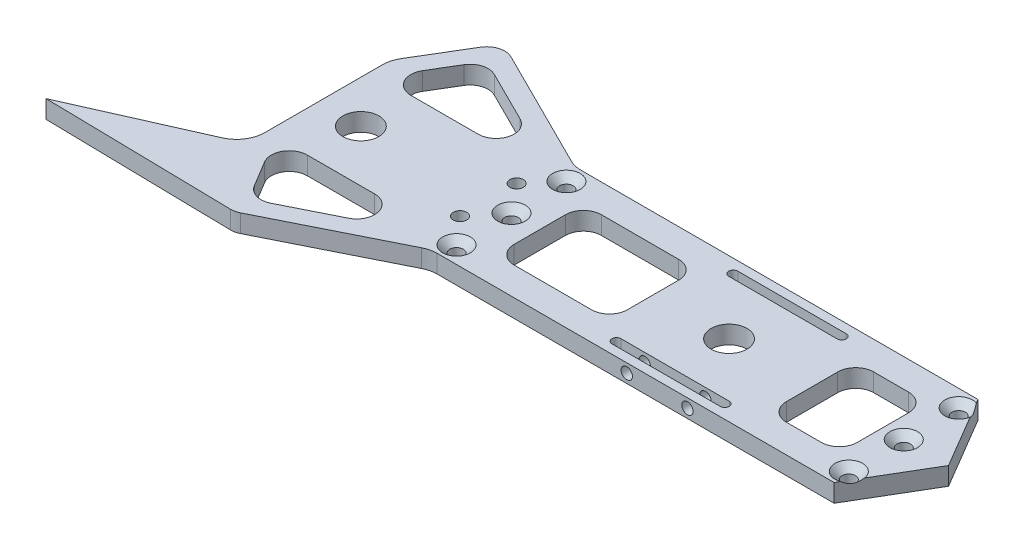
SolidWorks part; units mm, degrees
material "AISI 1020"
ref_plane "Alzado" through (0, 0, 0) normal (0, 0, 1) x (1, 0, 0)
ref_plane "Planta" through (0, 0, 0) normal (0, 1, 0) x (1, 0, 0)
ref_plane "Vista lateral" through (0, 0, 0) normal (1, 0, 0) x (0, 0, -1)
sketch "Croquis1" plane through (0, 0, 0) normal (0, 1, 0) x (1, 0, 0)
  line L0 (37.5, -25.4) -> (52.5, 0)
  line L3 (-45.9466, -25.4) -> (37.5, -25.4) construction
  line L4 (37.5, 25.4) -> (37.5, -25.4) construction
  line L5 (52.5, 0) -> (37.5, 25.4)
  line L6 (0, 0) -> (37.5, 0) construction
  line L11 (0, 0) -> (0, -19.05) construction
  line L12 (-19.05, 19.05) -> (19.05, 19.05) construction
  line L13 (-19.05, 19.05) -> (-19.05, -19.05) construction
  line L14 (-19.05, -19.05) -> (19.05, -19.05) construction
  line L15 (19.05, 19.05) -> (19.05, -19.05) construction
  line L16 (37.5, 25.4) -> (-105, 25.4)
  line L20 (-105, -25.4) -> (37.5, -25.4)
  line L21 (0, 0) -> (-170, 0) construction
  line L24 (-3.261, -52.3986) -> (59.3724, -56.2966) construction
  line L38 (-105, -25.4) -> (-105, 25.4) construction
  line L41 (-105, -25.4) -> (-149.7468, -47.7317)
  line L42 (-158.0248, -45.3215) -> (-170, -25.4) construction
  line L43 (-170, -25.4) -> (-170, 25.4)
  line L44 (-170, 25.4) -> (-158.0248, 45.3215)
  line L45 (-149.7468, 47.7317) -> (-105, 25.4)
  line L46 (-155, -50.3534) -> (-155, 50.3534) construction
  line L47 (-170, 25.4) -> (-105, 25.4) construction
  line L48 (-105, -25.4) -> (-170, -25.4) construction
  line L49 (-170, -25.4) -> (-219.0316, -47.147)
  line L50 (-219.0316, -47.147) -> (-152.7022, -48.3989)
  line L51 (-173.3511, 48.4) -> (-113.9016, 48.4) construction
  line L52 (-129.0451, 30.3033) -> (-147.3292, 39.4283)
  line L53 (-155.6072, 37.0181) -> (-161.0924, 27.8931)
  line L54 (-155.65, 18.2716) -> (-131.8807, 18.2716)
  line L55 (-182.7394, 6.35) -> (-126.5741, 6.35) construction
  line L56 (-162, 48.4) -> (-162, -3.791) construction
  line L57 (-129.0451, -30.3033) -> (-147.3292, -39.4283)
  line L58 (-155.6072, -37.0181) -> (-161.0924, -27.8931)
  line L59 (-155.65, -18.2716) -> (-131.8807, -18.2716)
  line L60 (-135, 6.35) -> (-115, 6.35) construction
  line L61 (-115, -6.35) -> (-135, -6.35) construction
  circle A0 centre (0, 0) radius 6.35 construction
  circle A1 centre (0, 0) radius 52.5 construction
  circle A11 centre (-155, 0) radius 6.35
  circle A12 centre (-155, 0) radius 44.45 construction
  arc A13 (-149.7468, -47.7317) -> (-158.0248, -45.3215) centre (-152.5824, -42.05) cw construction
  arc A14 (-158.0248, 45.3215) -> (-149.7468, 47.7317) centre (-152.5824, 42.05) cw
  arc A15 (-152.7022, -48.3989) -> (-149.7468, -47.7317) centre (-152.5824, -42.05) ccw
  arc A16 (-129.0451, 30.3033) -> (-131.8807, 18.2716) centre (-131.8807, 24.6216) cw
  arc A17 (-161.0924, 27.8931) -> (-155.65, 18.2716) centre (-155.65, 24.6216) ccw
  arc A18 (-147.3292, 39.4283) -> (-155.6072, 37.0181) centre (-150.1648, 33.7466) ccw
  arc A19 (-129.0451, -30.3033) -> (-131.8807, -18.2716) centre (-131.8807, -24.6216) ccw
  arc A20 (-147.3292, -39.4283) -> (-155.6072, -37.0181) centre (-150.1648, -33.7466) cw
  arc A21 (-161.0924, -27.8931) -> (-155.65, -18.2716) centre (-155.65, -24.6216) cw
  arc A22 (-135, 6.35) -> (-135, -6.35) centre (-135, 0) ccw construction
  arc A23 (-115, -6.35) -> (-115, 6.35) centre (-115, 0) ccw construction
  circle A32 centre (-25, 0) radius 50.8 construction
  circle A33 centre (-25, 0) radius 6.35
  point P19 (19.05, 0)
  point P20 (-170, 0)
  dimension "D1" = 12.7
  dimension "D2" = 105
  dimension "D7" = 6.35
  dimension "D10" = 23
  dimension "D11" = 25
  dimension "D9" = 15
  dimension "D15" = 20
  dimension "D3" = 50
  dimension "D4" = 88.9
  dimension "D12" = 12.7
  dimension "D13" = 6.35
  dimension "D18" = 6.35
  dimension "D20" = 101.6
  dimension "D5" = 50.8
  dimension "D6" = 15
  dimension "D8" = 38.1
  dimension "D14" = 8
  dimension "D16" = 10
  dimension "D17" = 105
  dimension "D19" = 80
extrude "Saliente-Extruir1" add sketch "Croquis1" along normal blind 6.35
sketch "Croquis4" plane through (0, 6.35, 0) normal (0, 1, 0) x (1, 0, 0)
  line L0 (-105, -25.4) -> (37.5, -25.4) construction
  line L1 (-101.825, -25.4) -> (-105, -25.4) construction
  line L2 (-101.825, -25.4) -> (-101.825, 25.4) construction
  line L3 (-101.825, 25.4) -> (-105, 25.4) construction
  line L4 (-105, -25.4) -> (-105, 25.4) construction
  line L5 (37.5, 25.4) -> (-105, 25.4) construction
  line L6 (37.5, -25.4) -> (34.325, -25.4)
  line L7 (37.5, -25.4) -> (37.5, 25.4)
  line L8 (37.5, 25.4) -> (34.325, 25.4)
  line L9 (34.325, -25.4) -> (34.325, 25.4)
  dimension "D1" = 3.175
extrude "Cortar-Extruir1" [suppressed] cut sketch "Croquis4" along normal blind 3.175 from surface
fillet "Redondeo1" radius 10 4 edges at (-170, 3.175, -25.4) (-170, 3.175, 25.4) (-105, 3.175, -25.4) (-105, 3.175, 25.4)
sketch "Croquis5" plane through (0, 0, 0) normal (0, -1, 0) x (1, 0, 0)
  line L0 (-44.125, 22.225) -> (-5.875, 22.225)
  line L1 (-5.875, 19.05) -> (-44.125, 19.05)
  line L2 (-19.05, 19.05) -> (19.05, 19.05) construction
  line L3 (-25, 0) -> (-25, 19.05) construction
  line L4 (-19.05, 0) -> (37.5, 0) construction
  line L5 (0, 0) -> (-170, 0) construction
  line L6 (-5.875, -19.05) -> (-44.125, -19.05)
  line L7 (-44.125, -22.225) -> (-5.875, -22.225)
  arc A0 (-44.125, 22.225) -> (-44.125, 19.05) centre (-44.125, 20.6375) ccw
  arc A1 (-5.875, 19.05) -> (-5.875, 22.225) centre (-5.875, 20.6375) ccw
  arc A2 (-5.875, -19.05) -> (-5.875, -22.225) centre (-5.875, -20.6375) cw
  arc A3 (-44.125, -22.225) -> (-44.125, -19.05) centre (-44.125, -20.6375) cw
  dimension "D1" = 3.175
  dimension "D2" = 38.25
extrude "Cortar-Extruir2" cut sketch "Croquis5" against normal through all
sketch "Croquis6" plane through (0, 0, 0) normal (0, -1, 0) x (1, 0, 0)
  line L1 (-85.475, 15.4) -> (-58.175, 15.4)
  line L2 (-91.825, 9.05) -> (-91.825, -9.05)
  line L3 (-85.475, -15.4) -> (-58.175, -15.4)
  line L4 (-51.825, 9.05) -> (-51.825, -9.05)
  line L5 (10.675, 15.4) -> (22.975, 15.4)
  line L6 (4.325, 9.05) -> (4.325, -9.05)
  line L7 (10.675, -15.4) -> (22.975, -15.4)
  line L8 (29.325, 9.05) -> (29.325, -9.05)
  line L9 (34.325, 25.4) -> (34.325, -25.4) construction
  line L10 (37.5, -25.4) -> (-102.6433, -25.4) construction
  line L11 (-102.6433, 25.4) -> (37.5, 25.4) construction
  line L12 (-170, -22.6257) -> (-170, 18.8958) construction
  arc A0 (22.975, -15.4) -> (29.325, -9.05) centre (22.975, -9.05) ccw
  arc A1 (22.975, 15.4) -> (29.325, 9.05) centre (22.975, 9.05) cw
  arc A2 (10.675, 15.4) -> (4.325, 9.05) centre (10.675, 9.05) ccw
  arc A3 (4.325, -9.05) -> (10.675, -15.4) centre (10.675, -9.05) ccw
  arc A4 (-58.175, -15.4) -> (-51.825, -9.05) centre (-58.175, -9.05) ccw
  arc A5 (-58.175, 15.4) -> (-51.825, 9.05) centre (-58.175, 9.05) cw
  arc A6 (-91.825, -9.05) -> (-85.475, -15.4) centre (-85.475, -9.05) ccw
  arc A7 (-85.475, 15.4) -> (-91.825, 9.05) centre (-85.475, 9.05) ccw
  point P12 (29.325, -15.4)
  dimension "D1" = 6.35
  dimension "D2" = 78.175
  dimension "D3" = 40
  dimension "D4" = 10
  dimension "D5" = 10
  dimension "D6" = 25
  dimension "D7" = 5
extrude "Cortar-Extruir3" cut sketch "Croquis6" against normal through all
sketch "Croquis7" plane through (0, 0, 0) normal (0, -1, 0) x (1, 0, 0)
  line L0 (-101.825, -25.4) -> (-101.825, 25.4) construction
  line L1 (37.5, -25.4) -> (-102.6433, -25.4) construction
  line L2 (-102.6433, 25.4) -> (37.5, 25.4) construction
  line L3 (-32.5716, -25.4) -> (-32.5716, 25.4) construction
  line L4 (36.6817, -25.4) -> (36.6817, 25.4) construction
  line L6 (37.5, -25.4) -> (-102.6433, -25.4) construction
  line L7 (-102.6433, 25.4) -> (37.5, 25.4) construction
  line L8 (-91.825, 9.05) -> (-91.825, -9.05) construction
  circle A0 centre (-101.825, 0) radius 2.3813
  circle A1 centre (-101.825, 19.4) radius 2.3813
  circle A2 centre (-101.825, -19.4) radius 2.3813
  circle A3 centre (36.6817, -19.4) radius 2.3813
  circle A4 centre (36.6817, 19.4) radius 2.3813
  circle A5 centre (36.6817, 0) radius 2.3812
  dimension "D1" = 4.7625
  dimension "D2" = 6
  dimension "D3" = 6
  dimension "D4" = 10
extrude "Cortar-Extruir4" cut sketch "Croquis7" against normal through all
sketch "Croquis8" plane through (0, 0, 0) normal (0, -1, 0) x (1, 0, 0)
  line L0 (0, 0) -> (-110, 0) construction
  line L1 (-110, 10) -> (-110, -10)
  circle A0 centre (-110, -10) radius 2.3813
  circle A1 centre (-110, 10) radius 2.3813
  dimension "D1" = 20
  dimension "D2" = 4.7625
  dimension "D3" = 110
extrude "Cortar-Extruir5" cut sketch "Croquis8" against normal through all contours A1 | A0 region at (-111.6362, 0, 11.6362)
sketch "Croquis9" plane through (0, 0, 25.4) normal (0, 0, 1) x (1, 0, 0)
  line L0 (37.5, 3.175) -> (-102.6433, 3.175) construction
  line L1 (37.5, 6.35) -> (37.5, 0) construction
  line L2 (-102.6433, 6.35) -> (-102.6433, 0) construction
  circle A0 centre (-14.2875, 3.175) radius 2
  circle A1 centre (-35.7125, 3.175) radius 2
  dimension "D3" = 4
  dimension "D1" = 10
  dimension "D2" = 10
extrude "Cortar-Extruir6" cut sketch "Croquis9" against normal blind 15
chamfer "Chaflán1" distance 2.5 angle 45 6 edges at (36.6817, 6.35, 21.7813) (36.6817, 6.35, 2.3812) (36.6817, 6.35, -17.0188) (-101.825, 6.35, -21.7813) (-101.825, 6.35, 17.0188) (-101.825, 6.35, -2.3813)
